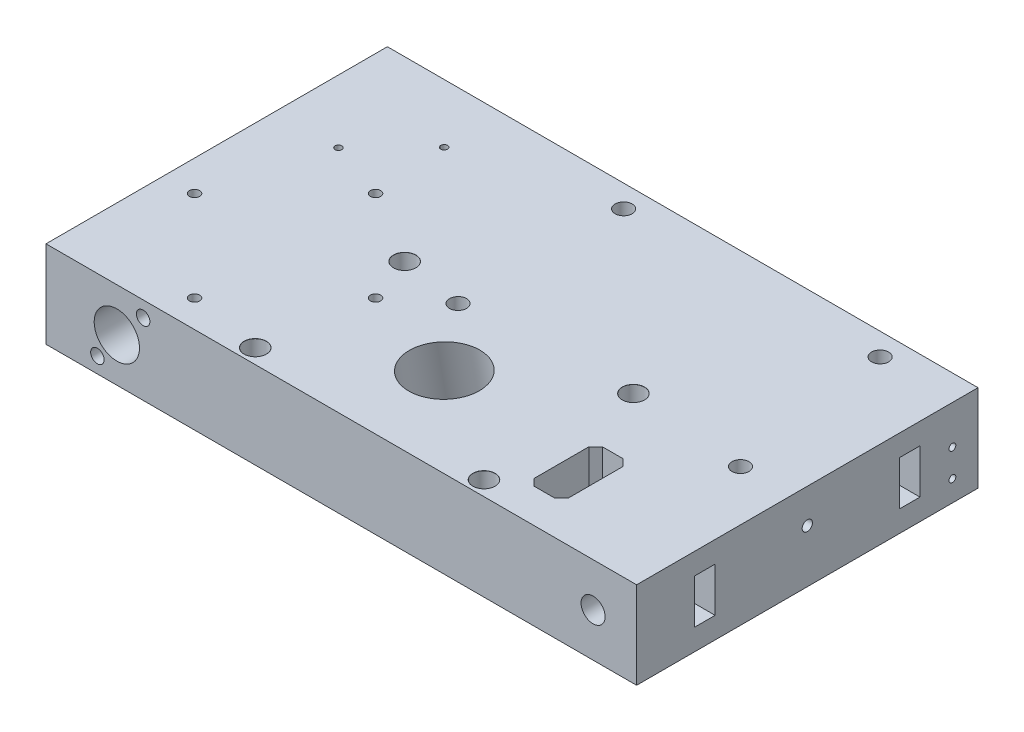
SolidWorks part; units mm, degrees
ref_plane "Front Plane" through (0, 0, 0) normal (0, 0, 1) x (1, 0, 0)
ref_plane "Top Plane" through (0, 0, 0) normal (0, 1, 0) x (1, 0, 0)
ref_plane "Right Plane" through (0, 0, 0) normal (1, 0, 0) x (0, 0, -1)
sketch "Sketch1" plane through (0, 0, 0) normal (0, 1, 0) x (1, 0, 0)
  line L1 (-82.5, -50) -> (82.5, -50)
  line L2 (-82.5, -50) -> (-82.5, 50)
  line L3 (-82.5, 50) -> (82.5, 50)
  line L4 (82.5, -50) -> (82.5, 50)
  line L5 (-82.5, -50) -> (82.5, 50) construction
  line L6 (-82.5, 50) -> (82.5, -50) construction
  point P0 (0, 0)
  dimension "D1" = 165
  dimension "D2" = 100
extrude "Boss-Extrude1" add sketch "Sketch1" along normal blind 12.75 and the other way blind 12.75
sketch "Sketch2" plane through (0, 0, 50) normal (0, 0, 1) x (1, 0, 0)
  line L0 (-82.5, 12.75) -> (-57, 12.75) construction
  line L1 (-82.5, 12.75) -> (82.5, 12.75) construction
  line L2 (-57, 12.75) -> (-57, -12.75) construction
  line L3 (-82.5, -12.75) -> (82.5, -12.75) construction
  line L4 (-57, -12.75) -> (-82.5, -12.75) construction
  line L5 (82.5, 12.75) -> (57, 12.75) construction
  line L6 (57, 12.75) -> (57, -12.75) construction
  line L7 (57, -12.75) -> (82.5, -12.75) construction
  line L8 (-82.5, 12.75) -> (-57, -12.75) construction
  line L9 (-57, 12.75) -> (-82.5, -12.75) construction
  line L10 (57, 12.75) -> (82.5, -12.75) construction
  line L11 (82.5, 12.75) -> (57, -12.75) construction
  line L12 (-69.75, 12.75) -> (-69.75, -12.75) construction
  line L13 (-69.75, 0) -> (-62.05, 0) construction
  line L14 (-62.05, 8.2) -> (-62.05, 0) construction
  circle A0 centre (-69.75, 0) radius 6.63
  circle A1 centre (69.75, 0) radius 3.525
  circle A3 centre (-75.45, -8.2) radius 1.975
  circle A5 centre (-62.05, 8.2) radius 1.975
  dimension "D3" = 13.26
  dimension "D4" = 7.05
  dimension "D5" = 8.2
  dimension "D1" = 25.5
  dimension "D2" = 25.5
  dimension "D7" = 7.7
sketch "Sketch3" plane through (0, 12.75, 0) normal (0, 1, 0) x (1, 0, 0)
  line L0 (0, 50) -> (0, 46) construction
  line L1 (82.5, 50) -> (-82.5, 50) construction
  line L2 (60.37, 46) -> (60.37, 43.46) construction
  line L3 (72.8, 46) -> (72.8, -7.34) construction
  line L4 (-15, -7.34) -> (-15, -4.8) construction
  line L5 (-28.8, -7.34) -> (-28.8, 46) construction
  line L6 (-14.76, 46) -> (0, 46) construction
  line L7 (-28.8, 46) -> (-14.76, 46) construction
  line L8 (-14.76, 46) -> (-14.76, 43.46) construction
  line L9 (-28.8, 46) -> (60.37, 46) construction
  line L10 (60.37, 46) -> (72.8, 46) construction
  line L11 (-28.8, -7.34) -> (-15, -7.34) construction
  line L12 (-28.8, -7.34) -> (36.7, -7.34) construction
  line L13 (36.7, -7.34) -> (36.7, -0.9) construction
  line L14 (-28.8, -7.34) -> (67.72, -7.34) construction
  line L15 (67.72, -7.34) -> (67.72, -4.8) construction
  line L16 (67.72, -7.34) -> (72.8, -7.34) construction
  line L17 (82.5, -50) -> (82.5, 50) construction
  line L18 (-82.5, 43.46) -> (-14.76, 43.46) construction
  line L19 (-82.5, 50) -> (-82.5, -50) construction
  line L20 (-14.76, 43.46) -> (60.37, 43.46) construction
  circle A0 centre (-14.76, 43.46) radius 2.5
  circle A1 centre (60.37, 43.46) radius 2.5
  circle A2 centre (-15, -4.8) radius 2.5
  circle A3 centre (36.7, -0.9) radius 2.5
  circle A4 centre (67.72, -4.8) radius 2.5
  point P30 (-14.76, 43.46)
  point P31 (-15, -4.8)
  point P32 (36.7, -0.9)
  point P33 (67.72, -4.8)
  point P34 (60.37, 43.46)
  dimension "D1" = 5
  dimension "D2" = 5
  dimension "D3" = 5
  dimension "D4" = 5
  dimension "D5" = 5
  dimension "D6" = 9.7
  dimension "D7" = 14.78
  dimension "D8" = 22.13
  dimension "D9" = 45.8
  dimension "D10" = 97.26
  dimension "D11" = 97.5
  dimension "D12" = 111.3
  dimension "D13" = 50.9
  dimension "D14" = 2.54
  dimension "D15" = 4
  dimension "D16" = 50.8
sketch "Sketch5" plane through (82.5, 0, 0) normal (1, 0, 0) x (0, 0, -1)
  line L0 (-50, 0) -> (-30, 0) construction
  line L3 (-50, -12.75) -> (-50, 12.75) construction
  line L4 (-30, 0) -> (-10, 0) construction
  line L5 (-10, 0) -> (10, 0) construction
  line L6 (10, 0) -> (30, 0) construction
  line L7 (30, 0) -> (50, 0) construction
  line L8 (-30, 0) -> (-30, 6.5) construction
  line L12 (30, 0) -> (30, 6.5) construction
  line L13 (-30, 6.5) -> (-27, 6.5) construction
  line L16 (30, 6.5) -> (33, 6.5) construction
  line L17 (50, -12.75) -> (50, 12.75) construction
  line L18 (-33, -6.5) -> (-27, -6.5)
  line L19 (-33, -6.5) -> (-33, 6.5)
  line L20 (-33, 6.5) -> (-27, 6.5)
  line L21 (-27, -6.5) -> (-27, 6.5)
  line L22 (-33, -6.5) -> (-27, 6.5) construction
  line L23 (-33, 6.5) -> (-27, -6.5) construction
  line L36 (27, -6.5) -> (33, -6.5)
  line L37 (27, -6.5) -> (27, 6.5)
  line L38 (27, 6.5) -> (33, 6.5)
  line L39 (33, -6.5) -> (33, 6.5)
  line L42 (-50, 12.75) -> (50, 12.75) construction
  dimension "D1" = 17
  dimension "D2" = 20
  dimension "D3" = 19.25
extrude "Cut-Extrude3" cut sketch "Sketch5" against normal blind 19.25
ref_plane "Plane1" through (0, 20.916, 3.6881) normal (0, 0.9848, 0.1736) x (1, 0, 0)
sketch "Sketch6" plane through (0, 20.916, 3.6881) normal (0, 0.9848, 0.1736) x (1, 0, 0)
  line L0 (0, -47.0264) -> (0, -21.2491) construction
  line L1 (-82.5, -47.0264) -> (82.5, -47.0264) construction
  circle A0 centre (0, -21.2491) radius 10.25
  dimension "D1" = 20.5
  dimension "D2" = 25.7773
extrude "Cut-Extrude4" cut sketch "Sketch6" against normal through all
sketch "Sketch11" plane through (0, 12.75, 0) normal (0, 1, 0) x (1, 0, 0)
  line L0 (-41.7252, -2.2252) -> (-68.2417, -28.7417) construction
  line L1 (-54.9835, 11.033) -> (-81.5, -15.4835) construction
  line L2 (-81.5, -15.4835) -> (-54.9835, -42) construction
  line L3 (-82.5, 50) -> (-82.5, -50) construction
  line L4 (82.5, -50) -> (82.5, 50) construction
  line L5 (-82.5, -50) -> (82.5, -50) construction
  line L6 (82.5, 50) -> (-82.5, 50) construction
  line L9 (-27.4063, -14.4228) -> (-28.467, -15.4835) construction
  line L10 (-54.9835, -42) -> (-28.467, -15.4835) construction
  line L11 (-28.467, -15.4835) -> (-54.9835, 11.033) construction
  circle A0 centre (-28.467, -15.4835) radius 1.5
  circle A1 centre (-54.9835, -42) radius 1.5
  circle A3 centre (-54.9835, 11.033) radius 1.5
  circle A4 centre (-81.5, -15.4835) radius 1.5
  dimension "D4" = 3
  dimension "D5" = 3
  dimension "D3" = 3
  dimension "D6" = 3
  dimension "D7" = 37.5
  dimension "D8" = 8
  dimension "D1" = 45
  dimension "D2" = 37.5
  dimension "D9" = 1
extrude "Cut-Extrude6" cut sketch "Sketch11" against normal blind 5
extrude "Cut-Extrude7" cut sketch "Sketch2" against normal through all
extrude "Cut-Extrude8" cut sketch "Sketch3" against normal blind 5 contours A2 | A4 | A1 | A0 region at (-14.76, 12.75, -43.46) region at (60.37, 12.75, -43.46) region at (-15, 12.75, 4.8) region at (67.72, 12.75, 4.8)
sketch "Sketch12" plane through (0, 12.75, 0) normal (0, 1, 0) x (1, 0, 0)
  circle A0 centre (-56.672, 32.8) radius 0.985
  circle A1 centre (-72.039, 17.2) radius 0.985
  dimension "D1" = 1.97
  dimension "D2" = 1.97
extrude "Cut-Extrude9" cut sketch "Sketch12" against normal blind 5
other "Move Face1" face at (-82.5, 5.125, 7.7417) offset 8 parameters "D1"=8
sketch "Sketch13" plane through (0, 12.75, 0) normal (0, 1, 0) x (1, 0, 0)
  line L0 (-90.5, -50) -> (82.5, -50) construction
  line L1 (40.5, -20) -> (50.5, -20)
  line L2 (40.5, -20) -> (40.5, -40)
  line L3 (40.5, -40) -> (50.5, -40)
  line L4 (50.5, -20) -> (50.5, -40)
  line L5 (82.5, -50) -> (82.5, 50) construction
  dimension "D1" = 10
  dimension "D2" = 20
  dimension "D3" = 10
  dimension "D4" = 32
extrude "Cut-Extrude10" cut sketch "Sketch13" against normal through all
chamfer "Chamfer1" distance 2 angle 45 4 edges at (40.5, 0, 40) (50.5, 0, 40) (50.5, 0, 20) (40.5, 0, 20)
sketch "Sketch14" plane through (82.5, 0, 0) normal (1, 0, 0) x (0, 0, -1)
  circle A0 centre (0, 2.75) radius 1.5 construction
  circle A1 centre (0, 2.75) radius 1.5
extrude "Cut-Extrude11" cut sketch "Sketch14" against normal blind 5
sketch "Sketch15" plane through (-90.5, 0, 0) normal (-1, 0, 0) x (0, 0, 1)
  circle A0 centre (0, 2.75) radius 1.5 construction
  circle A1 centre (0, 2.75) radius 1.5
extrude "Cut-Extrude12" cut sketch "Sketch15" against normal blind 5
sketch "Sketch17" plane through (0, 12.75, 0) normal (0, 1, 0) x (1, 0, 0)
  line L0 (0, -13.4169) -> (0, -34.2332) construction
  line L1 (-10.25, -23.8251) -> (10.25, -23.8251) construction
  line L2 (0, -23.8251) -> (33.5, -23.8251) construction
  line L3 (33.5, -23.8251) -> (33.5, -1.9401) construction
  circle A0 centre (33.5, -1.9401) radius 1.5
  circle A1 centre (33.5, -45.7101) radius 1.5
  circle A2 centre (-33.5, -45.7101) radius 1.5
  circle A3 centre (-33.5, -1.9401) radius 1.5
  ellipse E0 centre (0, -23.8251) end of major axis (0, -13.4169) minor radius 10.25 construction
  dimension "D1" = 3
  dimension "D2" = 43.77
  dimension "D3" = 67
extrude "Cut-Extrude15" cut sketch "Sketch17" along normal through all from surface starting at face at (45.5, -12.75, 30)
sketch "Sketch18" plane through (0, -12.75, 0) normal (0, -1, 0) x (1, 0, 0)
  line L0 (62, -50) -> (62, -45) construction
  line L5 (82.5, -50) -> (-90.5, -50) construction
  line L6 (62, -45) -> (82.5, -45) construction
  line L7 (82.5, 50) -> (82.5, -50) construction
  line L8 (62, -45) -> (62, -17) construction
  line L9 (62, -17) -> (0, -17) construction
  line L10 (0, -17) -> (0, -45) construction
  line L11 (0, -45) -> (62, -45) construction
  line L12 (31, -45) -> (31, -38.46) construction
  line L13 (62, -31) -> (72, -31) construction
  line L14 (-14.76, -43.46) -> (60.37, -43.46) construction
  circle A0 centre (31, -38.46) radius 1.475
  circle A1 centre (72, -21) radius 1.5
  circle A2 centre (72, -41) radius 1.5
  circle A3 centre (-10, -21) radius 1.5
  circle A4 centre (-10, -41) radius 1.5
  dimension "D1" = 2.95
  dimension "D2" = 3
  dimension "D3" = 82
  dimension "D4" = 20
  dimension "D5" = 5
  dimension "D6" = 28
  dimension "D7" = 10.5
  dimension "D8" = 9
extrude "Cut-Extrude16" cut sketch "Sketch18" against normal blind 5
sketch "Sketch16" plane through (82.5, 0, 0) normal (1, 0, 0) x (0, 0, -1)
  line L0 (53.5082, -10.3101) -> (54.6824, -12.75) construction
  line L1 (53.5082, -10.3101) -> (54.6824, -12.75)
  circle A0 centre (42.5082, 1.41) radius 1.2 construction
  circle A1 centre (42.5082, -6.59) radius 1.2 construction
  circle A2 centre (42.5082, 1.41) radius 1.2
  circle A3 centre (42.5082, -6.59) radius 1.2
  circle A4 centre (42.5082, 1.41) radius 1
  circle A5 centre (42.5082, -6.59) radius 1
  dimension "D1" = 0.2
extrude "Cut-Extrude13" cut sketch "Sketch16" against normal blind 10 contours A5 | A4 region at (82.5, 1.41, -42.5082) region at (82.5, -6.59, -42.5082)
other "Move Face2" [suppressed] offset 5 parameters "D1"=5
hole_wizard "CBORE for M3 SHCS1" positions "Sketch20" profile "Sketch22" counterbore size "M3" standard "ANSI Metric" end condition through all
sketch "Sketch20" plane through (0, 12.75, 0) normal (0, 1, 0) x (1, 0, 0)
  point P0 (33.5, -1.9401)
  point P3 (33.5, -45.7101)
  point P6 (-33.5, -45.7101)
  point P9 (-33.5, -1.9401)
sketch "Sketch22" plane through (33.5, 12.75, 1.9401) normal (1, 0, 0) x (0, 0, 1)
  line L0 (0, 0) -> (0, 25.5)
  line L1 (0, 25.5) -> (1.8, 25.5)
  line L3 (1.8, 25.5) -> (1.8, 20)
  line L4 (3.25, 20) -> (1.8, 20)
  line L5 (3.25, 20) -> (3.25, 0.025)
  line L6 (3.25, 0.025) -> (3.275, 0)
  line L7 (3.275, 0) -> (0, 0)
  line L8 (-3.25, 0.025) -> (-3.275, 0) construction
  line L11 (0, -6.35) -> (0, 107.95) construction
  dimension "Thru Hole Dia." = 3.6
  dimension "Thru Hole Depth" = 25.5
  dimension "C'Bore Dia." = 6.5
  dimension "C'Bore Depth" = 20
  dimension "Near C'Sink Dia." = 6.55
  dimension "Near C'Sink Angle" = 90
